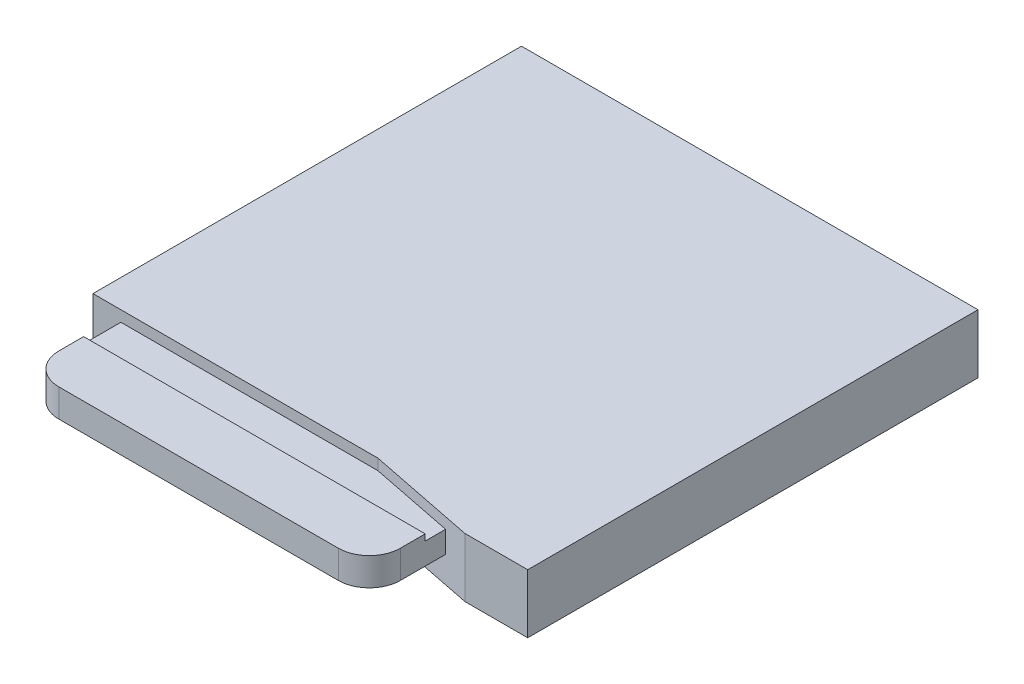
SolidWorks part; units mm, degrees
ref_plane "Front Plane" through (0, 0, 0) normal (0, 0, 1) x (1, 0, 0)
ref_plane "Top Plane" through (0, 0, 0) normal (0, 1, 0) x (1, 0, 0)
ref_plane "Right Plane" through (0, 0, 0) normal (1, 0, 0) x (0, 0, -1)
sketch "Sketch1" plane through (0, 0, 0) normal (0, 1, 0) x (1, 0, 0)
  line L1 (-7.35, -7.25) -> (7.35, -7.25)
  line L2 (-7.35, -7.25) -> (-7.35, 7.25)
  line L3 (-7.35, 7.25) -> (7.35, 7.25)
  line L4 (7.35, -7.25) -> (7.35, 7.25)
  line L5 (-7.35, -7.25) -> (7.35, 7.25) construction
  line L6 (-7.35, 7.25) -> (7.35, -7.25) construction
  point P0 (0, 0)
  dimension "D1" = 14.5
  dimension "D2" = 14.7
extrude "Boss-Extrude1" add sketch "Sketch1" along normal blind 1.9
sketch "Sketch2" plane through (0, 1.9, 0) normal (0, 1, 0) x (1, 0, 0)
  line L0 (-7.35, -6.55) -> (1.8249, -6.55)
  line L1 (-7.35, 7.25) -> (-7.35, -7.25) construction
  line L2 (1.8249, -6.55) -> (5.3285, -7.25)
  line L3 (-7.35, -7.25) -> (7.35, -7.25) construction
  line L4 (7.35, 7.25) -> (-7.35, 7.25) construction
  dimension "D1" = 13.8
extrude "Cut-Extrude1" cut sketch "Sketch2" against normal blind 1.9 and the other way through all flip side to cut
sketch "Sketch3" plane through (0, 0, 6.55) normal (0, 0, 1) x (1, 0, 0)
  line L1 (-6.45, 1.55) -> (4.55, 1.55)
  line L2 (-6.45, 1.55) -> (-6.45, 0.85)
  line L3 (-6.45, 0.85) -> (4.55, 0.85)
  line L4 (4.55, 1.55) -> (4.55, 0.85)
  line L5 (0, 1.9) -> (0, 48.4827) construction
  line L6 (7.35, 1.9) -> (-7.35, 1.9) construction
  line L7 (-0.95, 1.55) -> (-0.95, 0.85) construction
  line L8 (1.8249, 0) -> (-7.35, 0) construction
  point P10 (0, 1.9)
  dimension "D1" = 0.7
  dimension "D2" = 11
  dimension "D3" = 0.85
  dimension "D4" = 0.95
extrude "Boss-Extrude2" add sketch "Sketch3" along normal blind 3
sketch "Sketch4" plane through (0, 1.55, 0) normal (0, 1, 0) x (1, 0, 0)
  line L0 (4.55, -9.55) -> (4.55, -7.0945) construction
  line L1 (-6.45, -9.55) -> (4.55, -9.55)
  line L2 (-6.45, -9.55) -> (-6.45, -7.75)
  line L3 (-6.45, -7.75) -> (4.55, -7.75)
  line L4 (4.55, -9.55) -> (4.55, -7.75)
  dimension "D1" = 1.8
extrude "Boss-Extrude3" add sketch "Sketch4" along normal blind 0.2
fillet "Fillet1" radius 1 2 edges at (-6.45, 1.3, 9.55) (4.55, 1.3, 9.55)
sketch "Sketch5" plane through (0, 0, 0) normal (0, -1, 0) x (1, 0, 0)
  line L0 (0, -7.25) -> (0, 10.8932) construction
  line L1 (7.35, -7.25) -> (-7.35, -7.25) construction
  line L3 (5.3285, 7.25) -> (7.35, 7.25) construction
  circle A0 centre (-4.95, 3.25) radius 0.4
  circle A1 centre (3.05, 3.25) radius 0.4
  dimension "D1" = 0.8
  dimension "D2" = 4.95
  dimension "D3" = 3.05
  dimension "D4" = 4
extrude "Boss-Extrude4" add sketch "Sketch5" along normal blind 0.55
fillet "Fillet2" radius 0.1 2 edges at (3.05, -0.55, 2.85) (-4.95, -0.55, 2.85)
